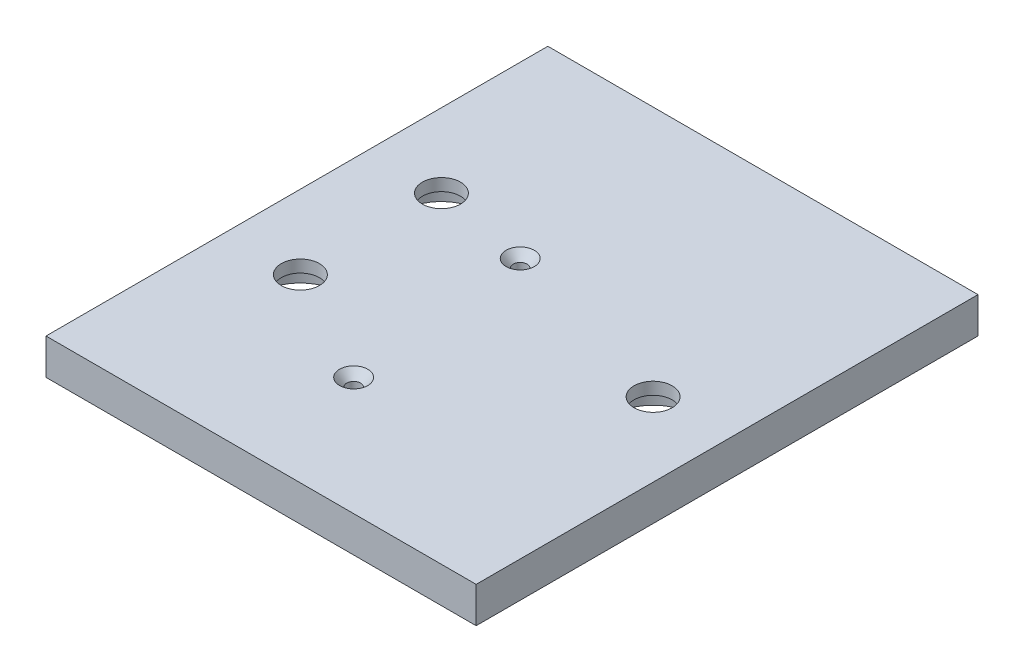
SolidWorks part; units mm, degrees
material "6061-T4 (SS)"
ref_plane "Front Plane" through (0, 0, 0) normal (0, 0, 1) x (1, 0, 0)
ref_plane "Top Plane" through (0, 0, 0) normal (0, 1, 0) x (1, 0, 0)
ref_plane "Right Plane" through (0, 0, 0) normal (1, 0, 0) x (0, 0, -1)
sketch "Sketch1" plane through (0, 0, 0) normal (0, 1, 0) x (1, 0, 0)
  line L1 (0, 0) -> (76.2, 0)
  line L2 (0, 0) -> (0, 88.9)
  line L3 (0, 88.9) -> (76.2, 88.9)
  line L4 (76.2, 0) -> (76.2, 88.9)
  dimension "D1" = 76.2
  dimension "D2" = 88.9
extrude "Boss-Extrude1" add sketch "Sketch1" along normal blind 6.35
hole_wizard "CSK for #2 Flat Head Socket Cap Screw1" positions "Sketch4" profile "Sketch5" countersink size "#2" standard "ANSI Inch"
sketch "Sketch4" plane through (0, 6.35, 0) normal (0, 1, 0) x (1, 0, 0)
  circle A2 centre (33.6, 20.9) radius 0.889 construction
  circle A3 centre (30.1, 53.9) radius 0.889 construction
  point P0 (33.6, 20.9)
  point P2 (30.1, 53.9)
  point P11 (0, 0)
  point P12 (0, 0)
  point P15 (0, 0)
  point P18 (0, 0)
sketch "Sketch5" plane through (33.6, 6.35, -20.9) normal (1, 0, 0) x (0, 0, 1)
  line L0 (0, 0) -> (0, 7.1326)
  line L1 (0, 7.1326) -> (1.2192, 6.4)
  line L2 (1.2192, 6.4) -> (1.2192, 1.4756)
  line L3 (1.2192, 1.4756) -> (2.5019, 0)
  line L5 (2.5019, 0) -> (0, 0)
  line L6 (-1.2192, 1.4756) -> (-2.5019, 0) construction
  line L10 (0, 7.1326) -> (-1.2192, 6.4) construction
  line L11 (0, -6.35) -> (0, 107.95) construction
  dimension "Hole Dia." = 2.4384
  dimension "Hole Depth" = 6.4
  dimension "Near C'Sink Dia." = 5.0038
  dimension "Near C'Sink Angle" = 82
  dimension "Drill Angle" = 118
sketch "Sketch6" plane through (0, 6.35, 0) normal (0, 1, 0) x (1, 0, 0)
  line L0 (30.1, 20.9) -> (30.1, 53.9) construction
  line L1 (30.1, 20.9) -> (33.6, 20.9) construction
  point P4 (30.1, 43.9)
  dimension "D1" = 10
sketch "Sketch7" plane through (0, 0, 0) normal (0, -1, 0) x (1, 0, 0)
  line L0 (38.1, 0) -> (38.1, -88.9) construction
  line L3 (0, 0) -> (76.2, 0) construction
  line L4 (76.2, -88.9) -> (0, -88.9) construction
  point P6 (38.1, -44.45)
hole_wizard "CBORE for 1/4 Binding Head Machine Screw1" positions "Sketch8" profile "Sketch9" counterbore size "1/4" standard "ANSI Inch"
sketch "Sketch8" plane through (0, 0, 0) normal (0, -1, 0) x (-1, 0, 0)
  circle A0 centre (-13.1064, 31.9532) radius 3.302 construction
  circle A1 centre (-13.1064, 56.9468) radius 3.302 construction
  circle A2 centre (-63.0936, 44.45) radius 3.302 construction
  point P0 (-63.0936, 44.45)
  point P2 (-13.1064, 31.9532)
  point P4 (-13.1064, 56.9468)
sketch "Sketch9" plane through (63.0936, 0, -44.45) normal (1, 0, 0) x (0, 0, -1)
  line L0 (0, 0) -> (0, 8.4298)
  line L1 (0, 8.4298) -> (3.3782, 6.4)
  line L2 (3.3782, 6.4) -> (3.3782, 4.191)
  line L3 (3.3782, 4.191) -> (7.1437, 4.191)
  line L4 (7.1437, 4.191) -> (7.1437, 0)
  line L5 (7.1437, 0) -> (0, 0)
  line L10 (0, 8.4298) -> (-3.3782, 6.4) construction
  line L11 (0, -6.35) -> (0, 107.95) construction
  dimension "Hole Dia." = 6.7564
  dimension "Hole Depth" = 6.4
  dimension "C'Bore Dia." = 14.2875
  dimension "C'Bore Depth" = 4.191
  dimension "Drill Angle" = 118
